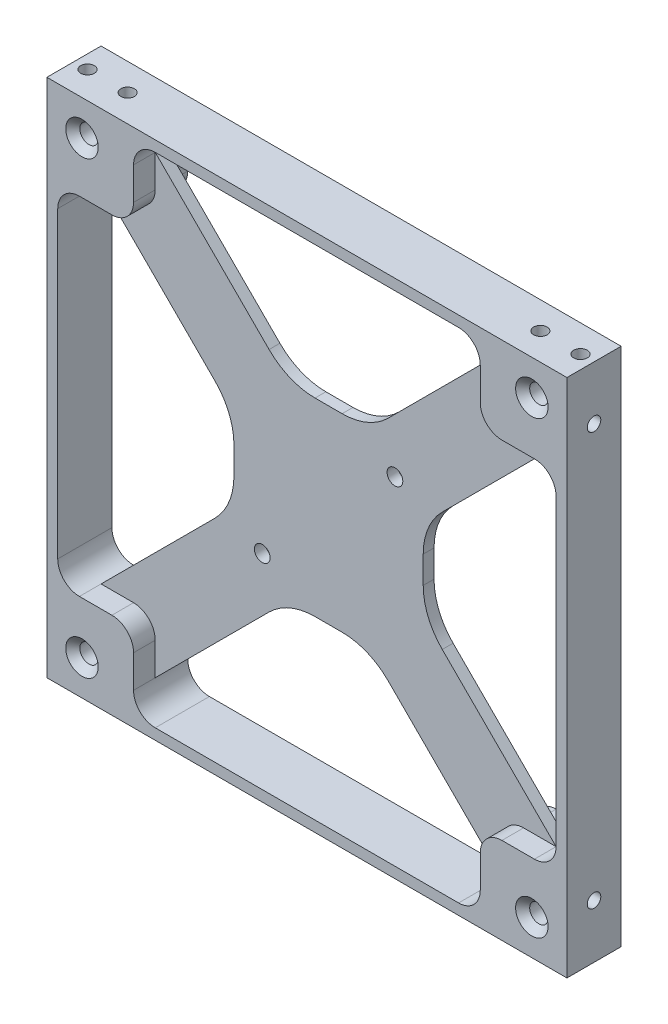
SolidWorks part; units mm, degrees
material "7075-T6 (SN)"
ref_plane "Front Plane" through (0, 0, 0) normal (0, 0, 1) x (1, 0, 0)
ref_plane "Top Plane" through (0, 0, 0) normal (0, 1, 0) x (1, 0, 0)
ref_plane "Right Plane" through (0, 0, 0) normal (1, 0, 0) x (0, 0, -1)
sketch "Construction Lines" plane through (0, 0, 0) normal (0, 0, 1) x (1, 0, 0)
  line L0 (0, 0) -> (0, -14.7163) construction
  line L1 (0, 0) -> (23.9312, 0) construction
sketch "Sketch3" plane through (0, 0, 0) normal (0, 0, 1) x (1, 0, 0)
  line L0 (0, 48) -> (48, 48)
  line L1 (0, 200000) -> (0, -200014.7163) construction
  line L2 (48, 48) -> (48, 0)
  line L3 (-200000, 0) -> (200023.9312, 0) construction
  line L4 (0, 46) -> (28, 46)
  line L5 (46, 28) -> (46, 0)
  line L6 (0, 48) -> (0, 46)
  line L7 (48, 0) -> (46, 0)
  line L8 (32, 42) -> (32, 36)
  line L9 (36, 32) -> (42, 32)
  line L11 (0, 46) -> (46, 46) construction
  line L12 (46, 46) -> (46, 0) construction
  arc A0 (28, 46) -> (32, 42) centre (28, 42) cw
  arc A1 (32, 36) -> (36, 32) centre (36, 36) ccw
  arc A2 (46, 28) -> (42, 32) centre (42, 28) ccw
  dimension "D6" = 4
  dimension "D1" = 48
  dimension "D2" = 48
  dimension "D4" = 16
  dimension "D5" = 16
  dimension "D3" = 2
extrude "BottomLayer" add sketch "Sketch3" along normal blind 4
sketch "TopHolePosition" plane through (0, 0, 4) normal (0, 0, 1) x (1, 0, 0)
  line L0 (0, 0) -> (48, 48) construction
sketch "Sketch6" plane through (0, 0, 4) normal (0, 0, 1) x (1, 0, 0)
  line L0 (0, 17.4706) -> (0, 0)
  line L1 (0, 0) -> (17.4706, 0)
  line L3 (0, 17.4706) -> (2.5, 17.4706)
  line L4 (0, 0) -> (48, 48) construction
  line L6 (17.4706, 0) -> (17.4706, 2.5)
  line L7 (38, 48) -> (10.9853, 20.9853)
  line L8 (48, 38) -> (20.9853, 10.9853)
  line L15 (48, 48) -> (0, 48) construction
  line L16 (48, 0) -> (48, 48) construction
  line L17 (38, 48) -> (48, 48)
  line L18 (48, 48) -> (48, 38)
  arc A1 (20.9853, 10.9853) -> (17.4706, 2.5) centre (29.4706, 2.5) ccw
  arc A2 (10.9853, 20.9853) -> (2.5, 17.4706) centre (2.5, 29.4706) cw
  dimension "D1" = 2.5
  dimension "D2" = 2.5
  dimension "D4" = 12
extrude "MiddleLayer" add sketch "Sketch6" along normal blind 2
sketch "Sketch10" plane through (0, 0, 6) normal (0, 0, 1) x (1, 0, 0)
  line L8 (48, 48) -> (0, 48)
  line L9 (48, 0) -> (48, 48)
  line L10 (46, 0) -> (48, 0)
  line L11 (46, 28) -> (46, 0)
  line L12 (36, 32) -> (42, 32)
  line L13 (32, 42) -> (32, 36)
  line L14 (0, 46) -> (28, 46)
  line L15 (0, 48) -> (0, 46)
  line L16 (48, 48) -> (0, 48)
  line L17 (48, 0) -> (48, 48)
  line L18 (46, 0) -> (48, 0)
  line L19 (46, 28) -> (46, 0)
  line L20 (36, 32) -> (42, 32)
  line L21 (32, 42) -> (32, 36)
  line L22 (0, 46) -> (28, 46)
  line L23 (0, 48) -> (0, 46)
  arc A3 (46, 28) -> (42, 32) centre (42, 28) ccw
  arc A4 (46, 28) -> (42, 32) centre (42, 28) ccw
  arc A5 (32, 36) -> (36, 32) centre (36, 36) ccw
  arc A6 (32, 36) -> (36, 32) centre (36, 36) ccw
  arc A7 (32, 42) -> (28, 46) centre (28, 42) ccw
  arc A8 (32, 42) -> (28, 46) centre (28, 42) ccw
  dimension "D1" = 0
extrude "FillUpLayer" add sketch "Sketch10" against normal blind 2
sketch "Sketch11" plane through (0, 0, 6) normal (0, 0, 1) x (1, 0, 0)
  line L8 (48, 48) -> (0, 48)
  line L9 (48, 0) -> (48, 48)
  line L10 (46, 0) -> (48, 0)
  line L11 (46, 28) -> (46, 0)
  line L12 (36, 32) -> (42, 32)
  line L13 (32, 42) -> (32, 36)
  line L14 (0, 46) -> (28, 46)
  line L15 (0, 48) -> (0, 46)
  line L16 (48, 48) -> (0, 48)
  line L17 (48, 0) -> (48, 48)
  line L18 (46, 0) -> (48, 0)
  line L19 (46, 28) -> (46, 0)
  line L20 (36, 32) -> (42, 32)
  line L21 (32, 42) -> (32, 36)
  line L22 (0, 46) -> (28, 46)
  line L23 (0, 48) -> (0, 46)
  arc A3 (46, 28) -> (42, 32) centre (42, 28) ccw
  arc A4 (46, 28) -> (42, 32) centre (42, 28) ccw
  arc A5 (32, 36) -> (36, 32) centre (36, 36) ccw
  arc A6 (32, 36) -> (36, 32) centre (36, 36) ccw
  arc A7 (32, 42) -> (28, 46) centre (28, 42) ccw
  arc A8 (32, 42) -> (28, 46) centre (28, 42) ccw
  dimension "D1" = 0
extrude "TopLayer" add sketch "Sketch11" along normal blind 4
sketch "HolePosition" plane through (0, 0, 10) normal (0, 0, 1) x (1, 0, 0)
  line L0 (0, 41.525) -> (41.525, 41.525) construction
  line L1 (0, 200000) -> (0, -200014.7163) construction
  line L2 (0, 0) -> (48, 48) construction
  line L3 (41.525, 41.525) -> (41.525, 0) construction
  line L4 (-200000, 0) -> (200023.9312, 0) construction
  dimension "D1" = 41.525
hole_wizard "M3 Clearance Hole1" positions "Sketch13" profile "Sketch14" hole size "M3" standard "ISO" end condition through all
sketch "Sketch13" plane through (0, 0, 10) normal (0, 0, 1) x (1, 0, 0)
  point P0 (41.525, 41.525)
sketch "Sketch14" plane through (41.525, 41.525, 10) normal (1, 0, 0) x (0, -1, 0)
  line L0 (0, 0) -> (0, 10)
  line L1 (0, 10) -> (1.7, 10)
  line L2 (1.7, 10) -> (1.7, 1.3)
  line L3 (1.7, 1.3) -> (3, 0)
  line L5 (3, 0) -> (0, 0)
  line L6 (-1.7, 1.3) -> (-3, 0) construction
  line L11 (0, -6.35) -> (0, 107.95) construction
  dimension "Thru Hole Dia." = 3.4
  dimension "Thru Hole Depth" = 10
  dimension "Near C'Sink Dia." = 6
  dimension "Near C'Sink Angle" = 90
ref_axis "Axis1" through (0, 0, -0.5) along (0, 0, 1)
sketch "M2HolePositions" plane through (0, 0, 6) normal (0, 0, 1) x (1, 0, 0)
  line L0 (0, 0) -> (48, 48) construction
  line L1 (0, 200000) -> (0, -200014.7163) construction
  line L2 (0, 0) -> (6.9513, -6.9513) construction
  line L3 (-200000, 0) -> (200023.9312, 0) construction
  line L4 (0, 12.25) -> (12.25, 12.25) construction
  line L5 (12.25, 12.25) -> (12.25, 0) construction
  dimension "D1" = 45
  dimension "D3" = 12.25
hole_wizard "M2.5 Clearance Hole1" positions "Sketch24" profile "Sketch25" hole size "M2.5" standard "ISO" end condition through all
sketch "Sketch24" plane through (0, 0, 6) normal (0, 0, 1) x (1, 0, 0)
  point P0 (12.25, 12.25)
sketch "Sketch25" plane through (12.25, 12.25, 6) normal (1, 0, 0) x (0, -1, 0)
  line L0 (0, 0) -> (0, 6)
  line L1 (0, 6) -> (1.45, 6)
  line L2 (1.45, 6) -> (1.45, 0)
  line L5 (1.45, 0) -> (0, 0)
  line L11 (0, -6.35) -> (0, 107.95) construction
  dimension "Thru Hole Dia." = 2.9
  dimension "Thru Hole Depth" = 6
pattern_circular "CirPattern1" count 4 every 90 about axis through (0, 0, -0.5) along (0, 0, 1) of "TopLayer", "FillUpLayer", "MiddleLayer", "BottomLayer", "M3 Clearance Hole1"
sketch "SidePlate Hole ZY" plane through (48, 0, 0) normal (1, 0, 0) x (0, 0, -1)
  line L0 (-5, 48) -> (-5, -48) construction
  line L1 (-10, 48) -> (0, 48) construction
  line L2 (-10, -48) -> (0, -48) construction
  line L3 (-10, 38.1) -> (-5, 38.1) construction
  line L4 (-10, -48) -> (-10, 48) construction
  dimension "D1" = 9.9
sketch "SidePlate&RailHole ZX" plane through (0, 48, 0) normal (0, 1, 0) x (1, 0, 0)
  line L0 (48, -5) -> (-48, -5) construction
  line L1 (-48, -10) -> (-48, 0) construction
  line L2 (45.5, -10) -> (45.5, -5) construction
  line L5 (48, -10) -> (-48, -10) construction
  line L7 (38.1, -10) -> (38.1, -5) construction
  line L8 (48, -10) -> (48, 0) construction
  dimension "D1" = 2.5
  dimension "D2" = 9.9
hole_wizard "Tap Drill M3 Side Plate" positions "Sketch20" profile "Sketch21" hole size "M3" standard "ISO"
sketch "Sketch20" plane through (48, 0, 0) normal (1, 0, 0) x (0, 0, -1)
  point P0 (-5, 38.1)
sketch "Sketch21" plane through (48, 38.1, 5) normal (0, 1, 0) x (0, 0, -1)
  line L0 (0, 0) -> (0, 5.7511)
  line L1 (0, 5.7511) -> (1.25, 5)
  line L2 (1.25, 5) -> (1.25, 0)
  line L5 (1.25, 0) -> (0, 0)
  line L10 (0, 5.7511) -> (-1.25, 5) construction
  line L11 (0, -6.35) -> (0, 107.95) construction
  dimension "Hole Dia." = 2.5
  dimension "Hole Depth" = 5
  dimension "Drill Angle" = 118
ref_plane "MirrorPlaneForM2.5" through (0, 0, 0) normal (-0.7071, -0.7071, 0) x (0.7071, -0.7071, 0)
mirror "Camera Holes" about plane through (0, 0, 0) normal (-0.7071, -0.7071, 0) of "M2.5 Clearance Hole1"
hole_wizard "Tap Drill M3 Side Plate " positions "Sketch26" profile "Sketch27" hole size "M3" standard "ISO"
sketch "Sketch26" plane through (0, 48, 0) normal (0, 1, 0) x (1, 0, 0)
  point P0 (38.1, -5)
sketch "Sketch27" plane through (38.1, 48, 5) normal (1, 0, 0) x (0, 0, 1)
  line L0 (0, 0) -> (0, 5.7511)
  line L1 (0, 5.7511) -> (1.25, 5)
  line L2 (1.25, 5) -> (1.25, 0)
  line L5 (1.25, 0) -> (0, 0)
  line L10 (0, 5.7511) -> (-1.25, 5) construction
  line L11 (0, -6.35) -> (0, 107.95) construction
  dimension "Hole Dia." = 2.5
  dimension "Hole Depth" = 5
  dimension "Drill Angle" = 118
hole_wizard "Tap Drill M3 Rail" positions "Sketch28" profile "Sketch29" hole size "M3" standard "ISO"
sketch "Sketch28" plane through (0, 48, 0) normal (0, 1, 0) x (1, 0, 0)
  point P0 (45.5, -5)
sketch "Sketch29" plane through (45.5, 48, 5) normal (1, 0, 0) x (0, 0, 1)
  line L0 (0, 0) -> (0, 5.7511)
  line L1 (0, 5.7511) -> (1.25, 5)
  line L2 (1.25, 5) -> (1.25, 0)
  line L5 (1.25, 0) -> (0, 0)
  line L10 (0, 5.7511) -> (-1.25, 5) construction
  line L11 (0, -6.35) -> (0, 107.95) construction
  dimension "Hole Dia." = 2.5
  dimension "Hole Depth" = 5
  dimension "Drill Angle" = 118
mirror "SidePlate and Rail Holes 1" about plane through (0, 0, 0) normal (1, 0, 0) of "Tap Drill M3 Side Plate", "Tap Drill M3 Rail", "Tap Drill M3 Side Plate "
mirror "Side Plate and Rail Holes 2" about plane through (0, 0, 0) normal (0, 1, 0) of "SidePlate and Rail Holes 1"
